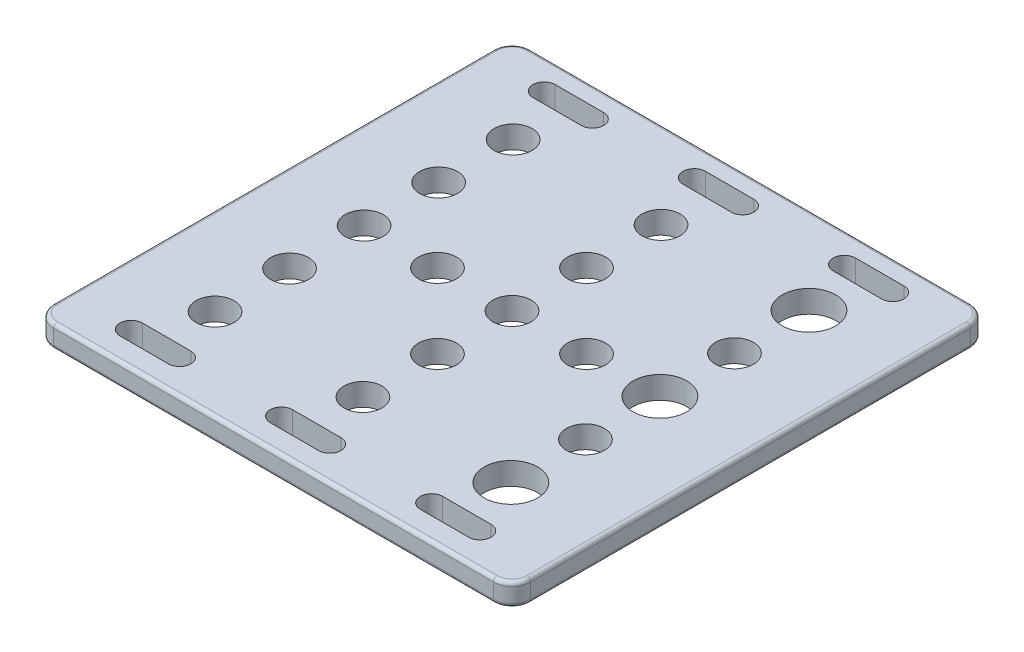
SolidWorks part; units mm, degrees
material "ABS"
ref_plane "Front Plane" through (0, 0, 0) normal (0, 0, 1) x (1, 0, 0)
ref_plane "Top Plane" through (0, 0, 0) normal (0, 1, 0) x (1, 0, 0)
ref_plane "Right Plane" through (0, 0, 0) normal (1, 0, 0) x (0, 0, -1)
sketch "Sketch1" plane through (0, 0, 0) normal (0, 1, 0) x (1, 0, 0)
  line L0 (-20.1, 20.25) -> (23.2, 20.25) construction
  line L1 (-20.1, -19.75) -> (19.6, -19.75) construction
  line L2 (29.5, 32) -> (-29.5, 32)
  line L3 (-32, 29.5) -> (-32, -29.5)
  line L4 (-29.5, -32) -> (29.5, -32)
  line L5 (32, -29.5) -> (32, 29.5)
  line L6 (3, 26.45) -> (-3.5, 26.45)
  line L7 (-23.65, 29.45) -> (-17.15, 29.45)
  line L8 (-17.15, 26.45) -> (-23.65, 26.45)
  line L9 (-3.5, 29.45) -> (3, 29.45)
  line L10 (16.65, 29.45) -> (23.15, 29.45)
  line L11 (23.15, 26.45) -> (16.65, 26.45)
  line L12 (-17.15, -28.95) -> (-23.65, -28.95)
  line L13 (-23.65, -25.95) -> (-17.15, -25.95)
  line L14 (-3.5, -25.95) -> (3, -25.95)
  line L15 (3, -28.95) -> (-3.5, -28.95)
  line L16 (23.15, -28.95) -> (16.65, -28.95)
  line L17 (16.65, -25.95) -> (23.15, -25.95)
  line L18 (-0.25, 0.25) -> (-0.25, -9.75) construction
  arc A0 (-29.5, 32) -> (-32, 29.5) centre (-29.5, 29.5) ccw
  arc A1 (-32, -29.5) -> (-29.5, -32) centre (-29.5, -29.5) ccw
  arc A2 (29.5, -32) -> (32, -29.5) centre (29.5, -29.5) ccw
  arc A3 (32, 29.5) -> (29.5, 32) centre (29.5, 29.5) ccw
  circle A4 centre (-10.25, 0.25) radius 2.55
  circle A5 centre (19.6, 0.25) radius 3.6
  arc A6 (-23.65, 29.45) -> (-23.65, 26.45) centre (-23.65, 27.95) ccw
  arc A7 (-17.15, 26.45) -> (-17.15, 29.45) centre (-17.15, 27.95) ccw
  arc A8 (-3.5, 29.45) -> (-3.5, 26.45) centre (-3.5, 27.95) ccw
  arc A9 (3, 26.45) -> (3, 29.45) centre (3, 27.95) ccw
  arc A10 (23.15, 26.45) -> (23.15, 29.45) centre (23.15, 27.95) ccw
  arc A11 (16.65, 29.45) -> (16.65, 26.45) centre (16.65, 27.95) ccw
  circle A12 centre (19.6, 10.25) radius 2.55
  circle A13 centre (-0.25, 10.25) radius 2.55
  arc A14 (-17.15, -28.95) -> (-17.15, -25.95) centre (-17.15, -27.45) ccw
  arc A15 (-23.65, -25.95) -> (-23.65, -28.95) centre (-23.65, -27.45) ccw
  arc A16 (-3.5, -25.95) -> (-3.5, -28.95) centre (-3.5, -27.45) ccw
  arc A17 (3, -28.95) -> (3, -25.95) centre (3, -27.45) ccw
  arc A18 (23.15, -28.95) -> (23.15, -25.95) centre (23.15, -27.45) ccw
  arc A19 (16.65, -25.95) -> (16.65, -28.95) centre (16.65, -27.45) ccw
  circle A20 centre (19.6, -19.75) radius 3.6
  circle A21 centre (-0.25, -9.75) radius 2.55
  circle A22 centre (19.6, -9.75) radius 2.55
  circle A23 centre (9.75, 0.25) radius 2.55
  circle A24 centre (-0.25, 0.25) radius 2.55
  circle A25 centre (-20.1, -19.75) radius 2.55
  circle A26 centre (-20.1, -9.75) radius 2.55
  circle A27 centre (-20.1, 0.25) radius 2.55
  circle A28 centre (-20.1, 10.25) radius 2.55
  circle A29 centre (19.6, 20.25) radius 3.6
  circle A30 centre (-20.1, 20.25) radius 2.55
  circle A31 centre (-0.25, -19.75) radius 2.55
  circle A32 centre (-0.25, 20.25) radius 2.55
extrude "Boss-Extrude1" add sketch "Sketch1" along normal blind 3
fillet "Fillet1" radius 0.5 16 edges at (31.2678, 0, 31.2678) (32, 0, 0) (31.2678, 0, -31.2678) (0, 0, -32) (-31.2678, 0, -31.2678) (-32, 0, 0) (-31.2678, 0, 31.2678) (0, 0, 32) (-32, 3, 0) (-31.2678, 3, 31.2678) (-31.2678, 3, -31.2678) (0, 3, -32) (31.2678, 3, -31.2678) (32, 3, 0) (31.2678, 3, 31.2678) (0, 3, 32)
